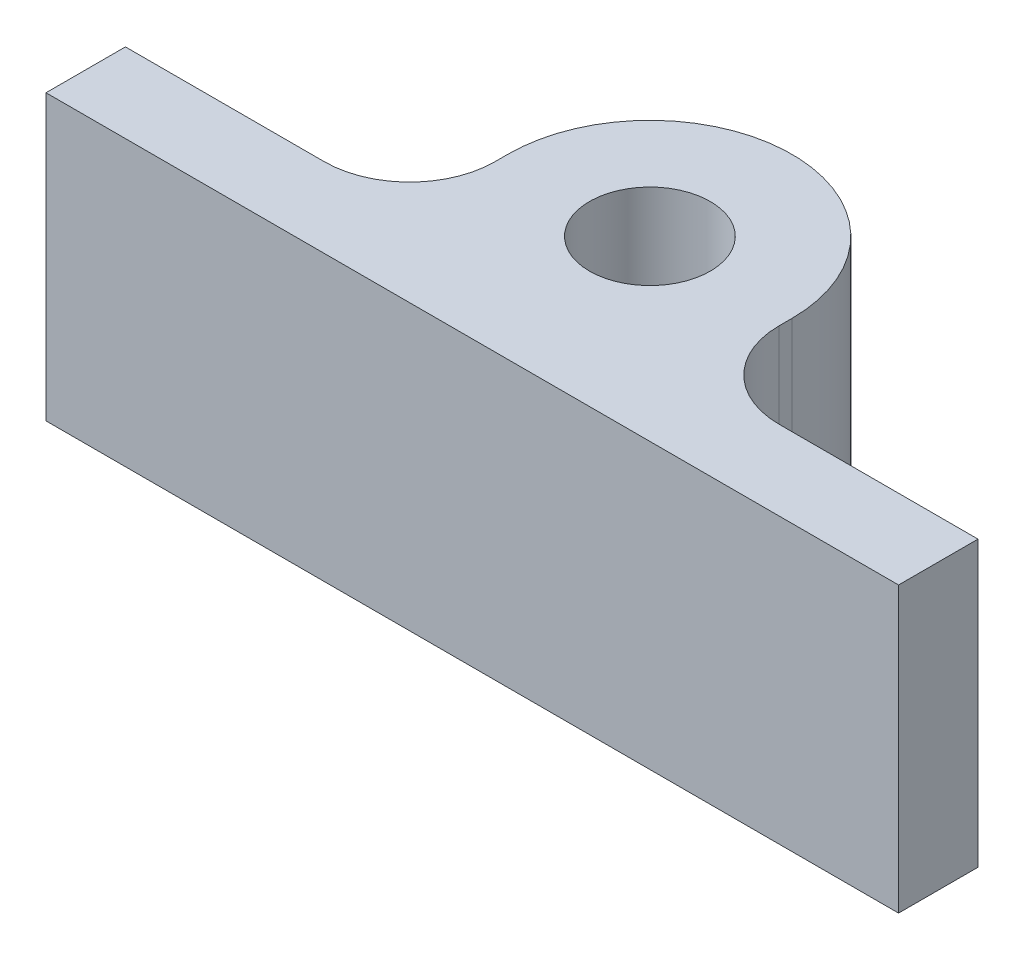
SolidWorks part; units mm, degrees
ref_plane "Front Plane" through (0, 0, 0) normal (0, 0, 1) x (1, 0, 0)
ref_plane "Top Plane" through (0, 0, 0) normal (0, 1, 0) x (1, 0, 0)
ref_plane "Right Plane" through (0, 0, 0) normal (1, 0, 0) x (0, 0, -1)
sketch "Sketch1" plane through (0, 0, 0) normal (0, 1, 0) x (1, 0, 0)
  line L0 (30, -12.5) -> (-30, -12.5)
  line L5 (-30, -12.5) -> (-30, -6.9096)
  line L7 (0, -47.9589) -> (0, -6.9096) construction
  line L8 (30, -12.5) -> (30, -6.9096)
  line L10 (-30, -6.9096) -> (-16, -6.9096)
  line L11 (-10, 0) -> (-10, -0.9096)
  line L12 (10, 0) -> (10, -0.9096)
  line L13 (16, -6.9096) -> (30, -6.9096)
  line L14 (0, -4.25) -> (0, 12.5) construction
  circle A0 centre (0, 0) radius 4.25
  arc A2 (10, 0) -> (-10, 0) centre (0, 0) ccw
  arc A3 (10, -0.9096) -> (16, -6.9096) centre (16, -0.9096) ccw
  arc A4 (-10, -0.9096) -> (-16, -6.9096) centre (-16, -0.9096) cw
  point P17 (10, -6.9096)
  dimension "D1" = 8.5
  dimension "D2" = 12.5
  dimension "D4" = 20
  dimension "D5" = 6
  dimension "D3" = 60
extrude "Boss-Extrude1" add sketch "Sketch1" along normal blind 20
